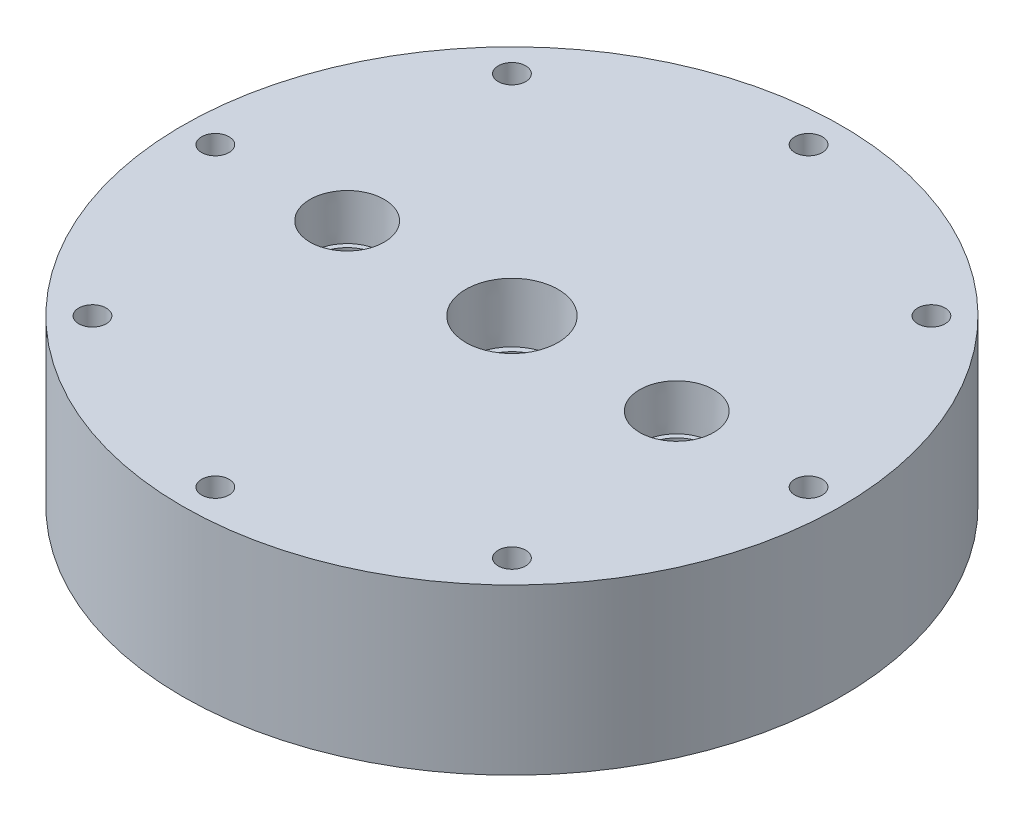
SolidWorks part; units mm, degrees
ref_plane "Front Plane" through (0, 0, 0) normal (0, 0, 1) x (1, 0, 0)
ref_plane "Top Plane" through (0, 0, 0) normal (0, 1, 0) x (1, 0, 0)
ref_plane "Right Plane" through (0, 0, 0) normal (1, 0, 0) x (0, 0, -1)
ref_axis "Axial" through (0, 53.34, 0) along (0, -1, 0)
ref_plane "Bottom Plane" through (0, -50.8, 0) normal (0, 1, 0) x (1, 0, 0)
sketch "Sketch1" plane through (0, 0, 0) normal (0, 1, 0) x (1, 0, 0)
  circle A0 centre (0, 0) radius 76.2
  dimension "D1" = 152.4
extrude "Billet" add sketch "Sketch1" against normal blind 50.8
sketch "Sketch3" plane through (0, -50.8, 0) normal (0, 1, 0) x (1, 0, 0)
  line L0 (0, 81.5114) -> (0, -83.2162) construction
  circle A0 centre (0, 0) radius 28.575
  dimension "D1" = 57.15
  dimension "D2" = 0
extrude "Lox Plate" cut sketch "Sketch3" along normal blind 17.78
sketch "Sketch5" plane through (0, -33.02, 0) normal (0, 1, 0) x (1, 0, 0)
  line L0 (0, 57.2178) -> (0, -49.9723) construction
  circle A0 centre (0, 0) radius 22.225
  dimension "D1" = 44.45
  dimension "D2" = 0
extrude "Lox Dome" cut sketch "Sketch5" along normal blind 4.4628
sketch "Sketch7" plane through (0, 0, 0) normal (0, 1, 0) x (1, 0, 0)
  circle A1 centre (0, 0) radius 76.2
  dimension "D2" = 152.4
extrude "Top Mill" cut sketch "Sketch7" against normal blind 12.7
sketch "Sketch11" plane through (0, -50.8, 0) normal (0, 1, 0) x (1, 0, 0)
  line L0 (0, 82.3071) -> (0, -82.946) construction
  circle A0 centre (0, 68.58) radius 3.175
  dimension "D1" = 6.35
  dimension "D2" = 68.58
extrude "1/4\" Bolt Hole" cut sketch "Sketch11" along normal up to next
pattern_circular "Bolt Pattern" count 8 over 360 about axis through (0, 53.34, 0) along (0, -1, 0) of "1/4\" Bolt Hole"
sketch "Sketch12" plane through (0, -50.8, 0) normal (0, 1, 0) x (1, 0, 0)
  circle A0 centre (0, 0) radius 60.96
  dimension "D1" = 121.92
extrude "Kerosene Plate" cut sketch "Sketch12" along normal blind 12.7
hole_wizard "Lox Inlet-1/2 NPT Tapped Hole3" positions "Sketch20" profile "Sketch21" size "1/2" standard "ANSI Inch" end condition through all
sketch "Sketch20" plane through (0, -12.7, 0) normal (0, 1, 0) x (1, 0, 0)
  line L0 (0, 40.1697) -> (0, -38.6779) construction
  point P8 (0, 0)
  dimension "D1" = 0
sketch "Sketch21" plane through (0, -12.7, 0) normal (1, 0, 0) x (0, 0, 1)
  line L0 (0, 0) -> (0, 38.1)
  line L1 (0, 38.1) -> (8.9281, 38.1)
  line L2 (-10.2617, 13.462) -> (-10.6647, 0) construction
  line L3 (8.9281, 38.1) -> (8.9281, 13.462)
  line L4 (8.9281, 13.462) -> (10.2617, 13.462)
  line L5 (10.2617, 13.462) -> (10.6647, 0)
  line L7 (10.6647, 0) -> (0, 0)
  line L8 (0, -6.35) -> (0, 107.95) construction
  line L11 (-8.9281, 13.462) -> (-10.2617, 13.462) construction
  dimension "Thru Tap Drill Dia." = 17.8562
  dimension "Thru Tap Drill Depth" = 38.1
  dimension "Thread Dia." = 21.3295
  dimension "Thread Angle" = 3.43
  dimension "Thread Depth" = 13.462
sketch "Sketch26" plane through (0, -33.02, 0) normal (0, -1, 0) x (1, 0, 0)
  line L0 (0, 56.6416) -> (0, -116.1839) construction
  circle A0 centre (0, 0) radius 25.4
  circle A1 centre (0, 0) radius 27.94
  dimension "D1" = 55.88
  dimension "D2" = 50.8
  dimension "D3" = 0
extrude "Lox Plate O Ring" cut sketch "Sketch26" against normal blind 2.032
hole_wizard "Kerosene Inlet-3/8 NPT Tapped Hole1" positions "Sketch24" profile "Sketch25" size "3/8" standard "ANSI Inch" end condition through all
sketch "Sketch24" plane through (0, -12.7, 0) normal (0, 1, 0) x (1, 0, 0)
  point P0 (-38.1, 0)
  point P2 (38.1, 0)
  dimension "D1" = 38.1
  dimension "D2" = 38.1
sketch "Sketch25" plane through (-38.1, -12.7, 0) normal (1, 0, 0) x (0, 0, 1)
  line L0 (0, 0) -> (0, 38.1)
  line L1 (0, 38.1) -> (7.1374, 38.1)
  line L2 (-8.2632, 10.414) -> (-8.575, 0) construction
  line L3 (7.1374, 38.1) -> (7.1374, 10.414)
  line L4 (7.1374, 10.414) -> (8.2632, 10.414)
  line L5 (8.2632, 10.414) -> (8.575, 0)
  line L7 (8.575, 0) -> (0, 0)
  line L8 (0, -6.35) -> (0, 107.95) construction
  line L11 (-7.1374, 10.414) -> (-8.2632, 10.414) construction
  dimension "Thru Tap Drill Dia." = 14.2748
  dimension "Thru Tap Drill Depth" = 38.1
  dimension "Thread Dia." = 17.15
  dimension "Thread Angle" = 3.43
  dimension "Thread Depth" = 10.414
sketch "Sketch27" plane through (0, -38.1, 0) normal (0, -1, 0) x (1, 0, 0)
  line L0 (0, 82.1632) -> (0, -90.1459) construction
  line L1 (20.955, 0) -> (-20.955, 0) construction
  circle A0 centre (0, 50.8) radius 1.1906
  circle A1 centre (0, -50.8) radius 1.1906
  dimension "D1" = 2.3813
  dimension "D2" = 50.8
extrude "Cut-Extrude1" cut sketch "Sketch27" against normal blind 3.175
